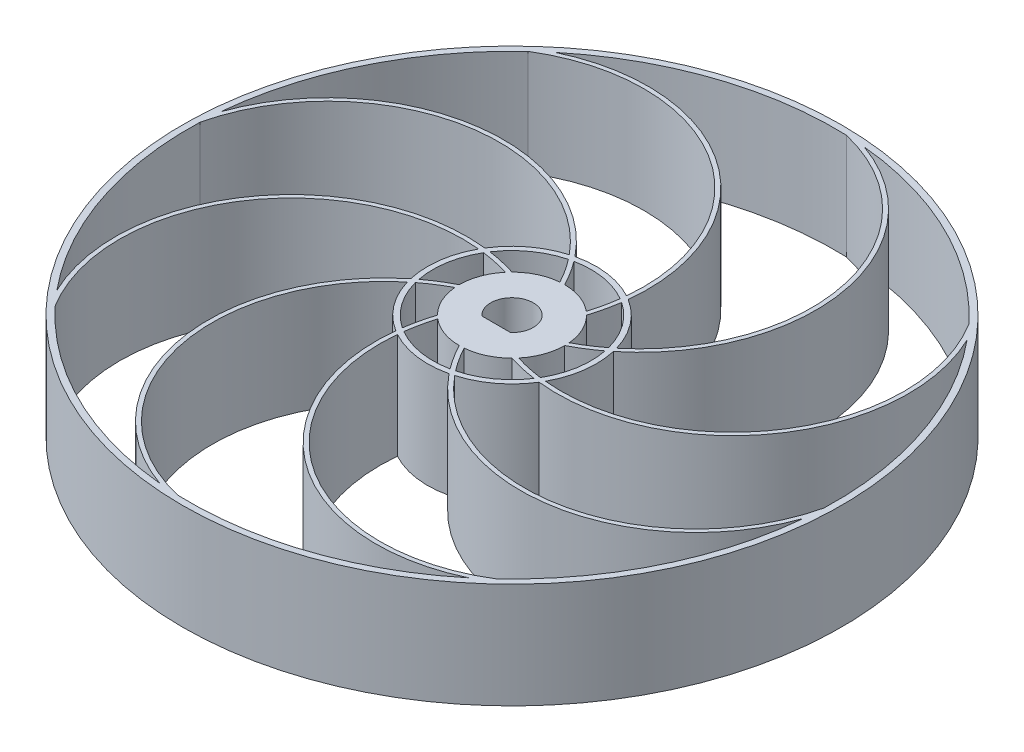
SolidWorks part; units mm, degrees
ref_plane "Front Plane" through (0, 0, 0) normal (0, 0, 1) x (1, 0, 0)
ref_plane "Top Plane" through (0, 0, 0) normal (0, 1, 0) x (1, 0, 0)
ref_plane "Right Plane" through (0, 0, 0) normal (1, 0, 0) x (0, 0, -1)
sketch "Sketch1" plane through (0, 0, 0) normal (0, 1, 0) x (1, 0, 0)
  line L0 (-2.7208, -3) -> (2.7208, -3)
  arc A0 (2.7208, -3) -> (-2.7208, -3) centre (0, 0) ccw
  circle A1 centre (0, 0) radius 62.5
  circle A28 centre (0, 0) radius 10
  circle A29 centre (0, 0) radius 61.3
  point P78 (0, 0)
  dimension "D1" = 8.1
  dimension "D2" = 125
  dimension "D3" = 20
  dimension "D7" = 3
  dimension "D4" = 1.2
extrude "Boss-Extrude1" add sketch "Sketch1" along normal blind 20 contours A1 A29 | A28 A0 L0 region at (-62.3232, 0, 0) region at (-9.7172, 0, 0)
sketch "Sketch4" plane through (0, 0, 0) normal (0, 1, 0) x (1, 0, 0)
  line L0 (-9.6325, -0.7106) -> (-10, 0)
  line L1 (0.1275, -61.7102) -> (0, -62.5)
  arc A0 (0, -62.5) -> (-10, 0) centre (5.3098, -29.6004) cw
  circle A1 centre (0, 0) radius 62.5 construction
  circle A2 centre (0, 0) radius 10 construction
  arc A3 (0.1275, -61.7102) -> (-9.6325, -0.7106) centre (5.3098, -29.6004) cw
  dimension "D1" = 0.8
extrude "Boss-Extrude4" add sketch "Sketch4" along normal up to surface (20 mm away) up to face at (0, 20, 61.3)
ref_axis "Axis1" through (0, 21, 0) along (0, -1, 0)
pattern_circular "CirPattern1" count 8 over 360 about axis through (0, 21, 0) along (0, -1, 0) of "Boss-Extrude4"
sketch "Sketch2" plane through (0, 0, 0) normal (0, 1, 0) x (1, 0, 0)
  circle A0 centre (0, 0) radius 15
  circle A1 centre (0, 0) radius 16
  dimension "D1" = 30
  dimension "D2" = 1
extrude "Boss-Extrude2" add sketch "Sketch2" along normal up to surface (20 mm away) up to face at (22.0804, 20, 26.8353)
sketch "Sketch3" plane through (0, 0, 0) normal (0, 1, 0) x (1, 0, 0)
  line L0 (0, -62.5) -> (0, -72.5)
  line L1 (-54.1266, -31.25) -> (-62.7868, -36.25)
  line L2 (-54.1266, 31.25) -> (-62.7868, 36.25)
  line L3 (0, 62.5) -> (0, 72.5)
  line L4 (54.1266, 31.25) -> (62.7868, 36.25)
  line L5 (54.1266, -31.25) -> (62.7868, -36.25)
  circle A0 centre (0, 0) radius 62.5 construction
  arc A1 (0, -72.5) -> (-15.8872, -60.4471) centre (-22.5214, -85.6888) ccw
  arc A2 (-15.8872, -60.4471) -> (0, -62.5) centre (0, 0) ccw
  arc A3 (-60.2923, -16.4648) -> (-54.1266, -31.25) centre (0, 0) ccw
  arc A4 (-62.7868, -36.25) -> (-60.2923, -16.4648) centre (-85.4694, -23.3403) ccw
  arc A5 (-44.4051, 43.9822) -> (-54.1266, 31.25) centre (0, 0) ccw
  arc A6 (-62.7868, 36.25) -> (-44.4051, 43.9822) centre (-62.948, 62.3485) ccw
  arc A7 (15.8872, 60.4471) -> (0, 62.5) centre (0, 0) ccw
  arc A8 (0, 72.5) -> (15.8872, 60.4471) centre (22.5214, 85.6888) ccw
  arc A9 (60.2923, 16.4648) -> (54.1266, 31.25) centre (0, 0) ccw
  arc A10 (62.7868, 36.25) -> (60.2923, 16.4648) centre (85.4694, 23.3403) ccw
  arc A11 (44.4051, -43.9822) -> (54.1266, -31.25) centre (0, 0) ccw
  arc A12 (62.7868, -36.25) -> (44.4051, -43.9822) centre (62.948, -62.3485) ccw
  circle A13 centre (0, 0) radius 62.5 construction
  circle A14 centre (0, 0) radius 62.5
  point P30 (0, 0)
  point P32 (0, 0)
  dimension "D1" = 10
extrude "Boss-Extrude3" add sketch "Sketch3" along normal up to surface (20 mm away) rebuild error yes up to face at (-10.3412, 20, 6.239)
